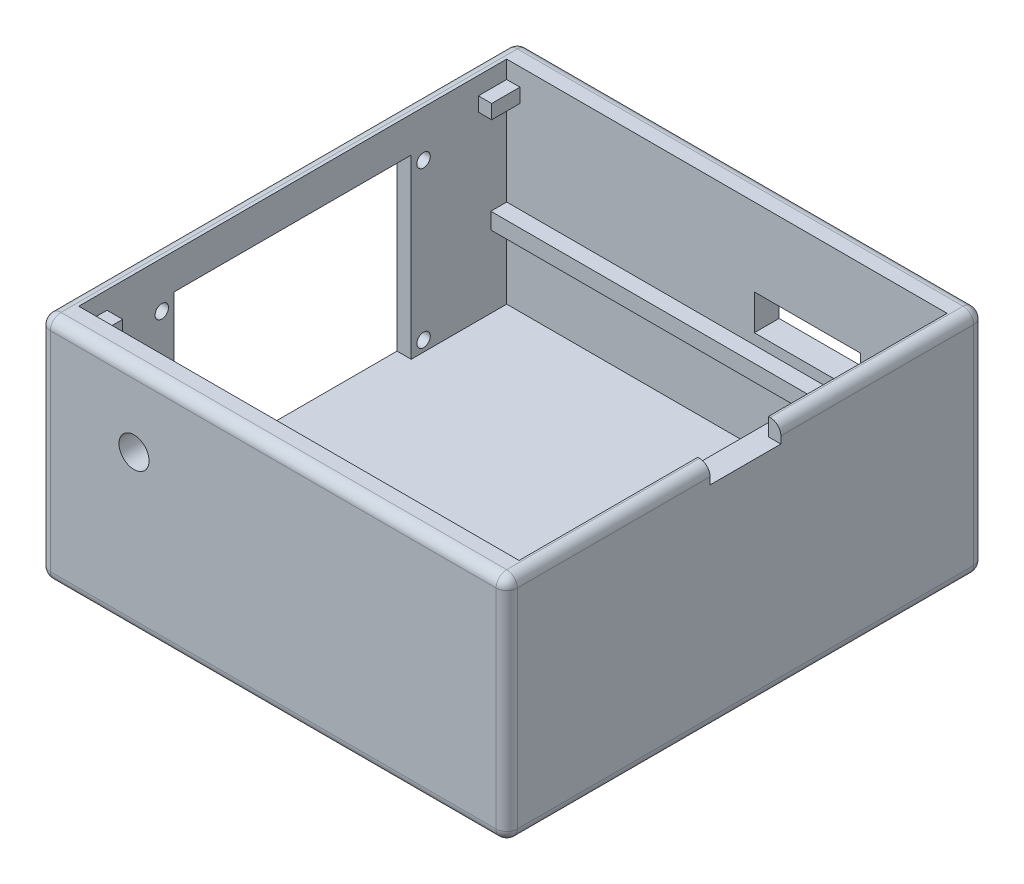
SolidWorks part; units mm, degrees
ref_plane "Front Plane" through (0, 0, 0) normal (0, 0, 1) x (1, 0, 0)
ref_plane "Top Plane" through (0, 0, 0) normal (0, 1, 0) x (1, 0, 0)
ref_plane "Right Plane" through (0, 0, 0) normal (1, 0, 0) x (0, 0, -1)
sketch "Sketch2" plane through (0, 0, 0) normal (0, 1, 0) x (1, 0, 0)
  line L0 (-60.5, 60.5) -> (-60.5, -60.5)
  line L1 (-67.5, 67.5) -> (67.5, 67.5)
  line L2 (-67.5, 67.5) -> (-67.5, -67.5)
  line L3 (-67.5, -67.5) -> (67.5, -67.5)
  line L4 (67.5, 67.5) -> (67.5, -67.5)
  line L5 (-67.5, 67.5) -> (67.5, -67.5) construction
  line L6 (-67.5, -67.5) -> (67.5, 67.5) construction
  line L7 (-60.5, -60.5) -> (60.5, -60.5)
  line L8 (60.5, 60.5) -> (60.5, -60.5)
  line L9 (-60.5, 60.5) -> (60.5, 60.5)
  point P0 (0, 0)
  dimension "D1" = 135
  dimension "D2" = 135
  dimension "D3" = 7
extrude "Boss-Extrude1" add sketch "Sketch2" along normal blind 65
extrude "Boss-Extrude2" add sketch "Sketch2<2>" along normal blind 5 contours L9 L0 L7 L8 region at (0, 0, 0)
sketch "Sketch2<2>" plane through (0, 0, 0) normal (0, 1, 0) x (1, 0, 0) same geometry as "Sketch2"
sketch "Sketch3" plane through (0, 0, -60.5) normal (0, 0, 1) x (1, 0, 0)
  line L1 (0, 0) -> (0, 65) construction
  line L2 (67.5, 0) -> (-67.5, 0) construction
  line L3 (60.5, 65) -> (-60.5, 65) construction
  line L4 (60.5, 65) -> (60.5, 5) construction
  line L5 (-60.5, 25.4157) -> (60.5, 25.4157)
  line L6 (-60.5, 25.4157) -> (-60.5, 30)
  line L7 (-60.5, 30) -> (60.5, 30)
  line L8 (60.5, 25.4157) -> (60.5, 30)
  line L9 (-60.5, 25.4157) -> (60.5, 30) construction
  line L10 (-60.5, 30) -> (60.5, 25.4157) construction
  line L11 (-60.5, 5) -> (60.5, 5) construction
  line L12 (-60.5, 65) -> (-60.5, 5) construction
  line L13 (9.5, 43) -> (39.5, 43)
  line L14 (9.5, 43) -> (9.5, 33)
  line L15 (9.5, 33) -> (39.5, 33)
  line L16 (39.5, 43) -> (39.5, 33)
  line L17 (9.5, 43) -> (39.5, 33) construction
  line L18 (9.5, 33) -> (39.5, 43) construction
  point P0 (-60.5, 24.6663)
  point P1 (0, 27.7078)
  point P16 (24.5, 38)
  dimension "D1" = 25
  dimension "D2" = 121
  dimension "D3" = 30
  dimension "D4" = 10
  dimension "D5" = 70
  dimension "D6" = 13
extrude "Boss-Extrude3" add sketch "Sketch3" along normal blind 4.5 contours L5 L8 L7 L6
extrude "Cut-Extrude1" cut sketch "Sketch3<3>" against normal through all contours L16 L13 L14 L15 region at (24.5, 38, -60.5)
sketch "Sketch3<3>" plane through (0, 0, -60.5) normal (0, 0, 1) x (1, 0, 0) same geometry as "Sketch3"
sketch "Sketch10" plane through (0, 0, 67.5) normal (0, 0, 1) x (1, 0, 0)
  circle A0 centre (-37.8514, 44.0831) radius 4.25
extrude "Cut-Extrude2" cut sketch "Sketch10" against normal blind 26.5 contours A0
sketch "Sketch11" plane through (-67.5, 0, 0) normal (-1, 0, 0) x (0, 0, 1)
  line L1 (-40, 5) -> (40, 5)
  line L2 (-40, 5) -> (-40, 55)
  line L3 (-40, 55) -> (40, 55)
  line L4 (40, 5) -> (40, 55)
  line L5 (-40, 5) -> (40, 55) construction
  line L6 (-40, 55) -> (40, 5) construction
  line L7 (-33.5, 55) -> (33.5, 55)
  line L8 (-33.5, 55) -> (-33.5, 5)
  line L9 (-33.5, 5) -> (33.5, 5)
  line L14 (0, 0) -> (0, 60) construction
  line L15 (-67.5, 0) -> (67.5, 0) construction
  line L16 (-67.5, 65) -> (67.5, 65) construction
  line L17 (0, 30) -> (67.5, 30) construction
  line L18 (67.5, 65) -> (67.5, 0) construction
  line L19 (33.5, 55) -> (33.5, 5)
  circle A0 centre (-37, 52) radius 1.9
  circle A1 centre (37, 52) radius 1.9
  circle A2 centre (37, 8) radius 1.9
  circle A3 centre (-37, 8) radius 1.9
  point P0 (0, 30)
  dimension "D2" = 3.8
  dimension "D1" = 3.5
extrude "Cut-Extrude3" cut sketch "Sketch11" against normal blind 26.5 contours L8 L7 L19 L9 | A0 | A2 | A1 | A3
sketch "Sketch12" plane through (0, 65, 0) normal (0, 1, 0) x (1, 0, 0)
  line L0 (67.5, -67.5) -> (67.5, 67.5) construction
  line L1 (60.5, 60.5) -> (67.5, 60.5)
  line L2 (60.5, 60.5) -> (60.5, -60.5)
  line L3 (60.5, -60.5) -> (67.5, -60.5)
  line L4 (67.5, 60.5) -> (67.5, -60.5)
extrude "Cut-Extrude4" cut sketch "Sketch12" against normal blind 5
sketch "Sketch13" plane through (0, 60, 0) normal (0, 1, 0) x (1, 0, 0)
  line L0 (64, 60.5) -> (64, -60.5)
  line L1 (67.5, 60.5) -> (60.5, 60.5) construction
  line L2 (60.5, -60.5) -> (67.5, -60.5) construction
  line L3 (64, -60.5) -> (67.5, -60.5)
  line L4 (67.5, -60.5) -> (67.5, 60.5)
  line L5 (67.5, 60.5) -> (64, 60.5)
extrude "Boss-Extrude4" add sketch "Sketch13" along normal blind 5
sketch "Sketch14" plane through (67.5, 0, 0) normal (1, 0, 0) x (0, 0, -1)
  line L0 (-10, 65) -> (10, 65)
  line L1 (-67.5, 65) -> (67.5, 65) construction
  line L2 (10, 65) -> (10, 60)
  line L3 (10, 60) -> (-10, 60)
  line L4 (-10, 60) -> (-10, 65)
  line L5 (-67.5, 65) -> (-67.5, 0) construction
  point P5 (0, 65)
  dimension "D1" = 57.5
  dimension "D2" = 5
extrude "Cut-Extrude5" cut sketch "Sketch14" against normal blind 5
sketch "Sketch15" plane through (-67.5, 0, 0) normal (-1, 0, 0) x (0, 0, 1)
  line L1 (-67.5, 0) -> (67.5, 0)
  line L2 (-67.5, 0) -> (-67.5, 65)
  line L3 (-67.5, 65) -> (67.5, 65)
  line L4 (67.5, 0) -> (67.5, 65)
extrude "Cut-Extrude6" cut sketch "Sketch15" against normal blind 3
sketch "Sketch16" plane through (0, 5, 0) normal (0, 1, 0) x (1, 0, 0)
  line L0 (-60.5, 0) -> (60.5, 0) construction
  line L1 (-60.5, 60.5) -> (-60.5, -60.5) construction
  line L2 (60.5, 60.5) -> (60.5, -60.5) construction
sketch "Sketch17" plane through (0, 0, 60.5) normal (0, 0, -1) x (-1, 0, 0)
  line L0 (0, 0) -> (0, 65) construction
  line L1 (-60.3877, 30) -> (60.5375, 30)
  line L2 (-60.3877, 30) -> (-60.3877, 25.5)
  line L3 (-60.3877, 25.5) -> (60.5375, 25.5)
  line L4 (60.5375, 30) -> (60.5375, 25.5)
  line L5 (60.5, 65) -> (-64, 65) construction
  point P9 (-60.3877, 4.8129)
  point P12 (0, 4.8129)
  dimension "D1" = 4.5
  dimension "D2" = 25.5
extrude "Boss-Extrude5" add sketch "Sketch17" along normal blind 4.5 contours L2 L1 L4 L3
sketch "Sketch18" plane through (0, 0, 0) normal (1, 0, 0) x (0, 0, -1)
fillet "Fillet1" radius 3 3 edges at (67.5, 0, 0) (1.5, 0, 67.5) (1.5, 0, -67.5)
fillet "Fillet2" radius 3 9 edges at (66.6213, 0.8787, -66.6213) (-64.5, 34, -67.5) (-64.5, 0.8787, -66.6213) (-64.5, 0, 0) (-64.5, 0.8787, 66.6213) (66.6213, 0.8787, 66.6213) (67.5, 34, -67.5) (-64.5, 34, 67.5) (67.5, 34, 67.5)
fillet "Fillet3" radius 3 9 edges at (67.5, 65, -37.25) (66.6213, 65, -66.6213) (1.5, 65, -67.5) (-63.6213, 65, -66.6213) (-64.5, 65, 0) (-63.6213, 65, 66.6213) (1.5, 65, 67.5) (66.6213, 65, 66.6213) (67.5, 65, 37.25)
sketch "Sketch19" plane through (0, 0, -60.5) normal (0, 0, 1) x (1, 0, 0)
  line L0 (-60.5, 65) -> (-60.5, 30) construction
  line L1 (-60.5, 60) -> (-56.7558, 60)
  line L2 (-60.5, 60) -> (-60.5, 56)
  line L3 (-60.5, 56) -> (-56.7558, 56)
  line L4 (-56.7558, 60) -> (-56.7558, 56)
  dimension "D1" = 5
  dimension "D2" = 4
extrude "Boss-Extrude6" add sketch "Sketch19" along normal blind 8
sketch "Sketch20" plane through (0, 0, 60.5) normal (0, 0, -1) x (-1, 0, 0)
  line L0 (60.5, 65) -> (60.5, 30) construction
  line L1 (60.5, 60) -> (56.0522, 60)
  line L2 (60.5, 60) -> (60.5, 55.348)
  line L3 (60.5, 55.348) -> (56.0522, 55.348)
  line L4 (56.0522, 60) -> (56.0522, 55.348)
  dimension "D1" = 5
  dimension "D2" = 4.4478
extrude "Boss-Extrude7" add sketch "Sketch20" along normal blind 8
